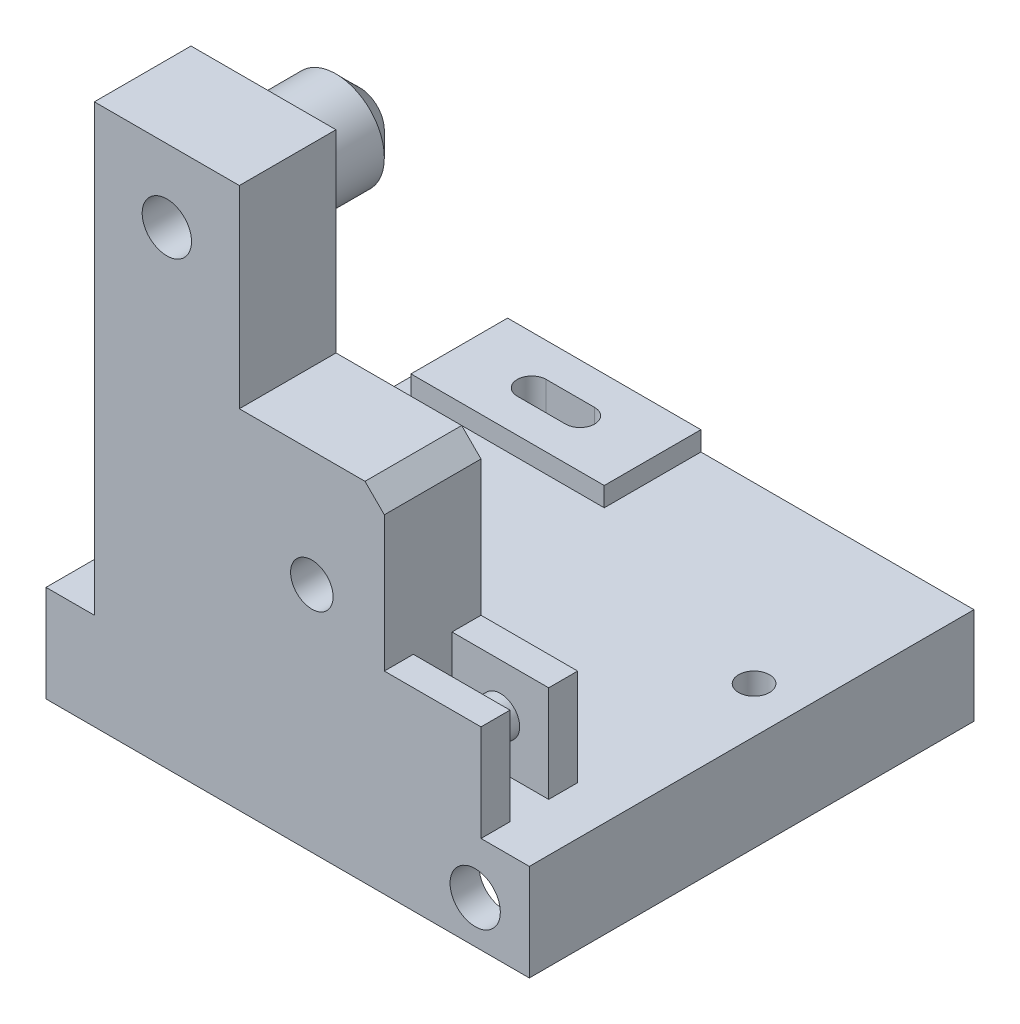
SolidWorks part; units mm, degrees
ref_plane "Front Plane" through (0, 0, 0) normal (0, 0, 1) x (1, 0, 0)
ref_plane "Top Plane" through (0, 0, 0) normal (0, 1, 0) x (1, 0, 0)
ref_plane "Right Plane" through (0, 0, 0) normal (1, 0, 0) x (0, 0, -1)
sketch "Sketch1" plane through (0, 0, 0) normal (0, 0, 1) x (1, 0, 0)
  line L0 (-15, 0) -> (-15, 46)
  line L1 (-15, 46) -> (0, 46)
  line L2 (0, 46) -> (0, 26)
  line L5 (0, 26) -> (15, 26)
  line L6 (15, 26) -> (15, 0)
  line L12 (-15, 0) -> (15, 0)
  circle A0 centre (-7.5, 38.5) radius 2.55
  circle A1 centre (7.5, 14) radius 2.2
  point P8 (0, 0)
  point P12 (-7.5, 46)
  point P16 (7.5, 26)
  dimension "D7" = 5.1
  dimension "D9" = 4.4
  dimension "D1" = 46
  dimension "D2" = 15
  dimension "D3" = 30
  dimension "D6" = 20
  dimension "D8" = 7.5
  dimension "D10" = 12
extrude "Boss-Extrude1" add sketch "Sketch1" along normal blind 6 and the other way blind 4
sketch "Sketch2" plane through (15, 0, 0) normal (1, 0, 0) x (0, 0, -1)
  line L0 (-6, 0) -> (4, 0) construction
  line L1 (-6, 0) -> (-6, 26) construction
  circle A0 centre (-1, 5) radius 2.5
  dimension "D1" = 5
  dimension "D2" = 5
  dimension "D3" = 5
extrude "Boss-Extrude2" [suppressed] add sketch "Sketch2" along normal blind 6
sketch "Sketch3" [suppressed] plane through (21, 0, 0) normal (1, 0, 0) x (0, 0, -1)
  circle A0 centre (-5, 5) radius 4.5
  circle A1 centre (-5, 5) radius 2.5
  circle A2 centre (-5, 5) radius 2.5 construction
  dimension "D1" = 0
  dimension "D2" = 2
extrude "Boss-Extrude3" [suppressed] add sketch "Sketch3" along normal blind 2
ref_plane "Plane1" through (0, 0, -4) normal (0, 0, -1) x (-1, 0, 0)
sketch "Sketch4" plane through (0, 0, -4) normal (0, 0, -1) x (-1, 0, 0)
  line L0 (-15, 0) -> (-15, 10)
  line L1 (-15, 0) -> (-25, 0)
  line L2 (-15, 10) -> (-25, 10)
  line L3 (-25, 0) -> (-25, 10)
  line L4 (-15, 0) -> (-15, 26) construction
  dimension "D1" = 10
  dimension "D2" = 10
extrude "Boss-Extrude4" add sketch "Sketch4" against normal blind 10
sketch "Sketch5" plane through (25, 0, 0) normal (1, 0, 0) x (0, 0, -1)
  line L0 (-3, 10) -> (1, 10)
  line L1 (-3, 10) -> (-3, 0)
  line L2 (1, 10) -> (1, 0)
  line L3 (-3, 0) -> (1, 0)
  line L4 (-6, 10) -> (4, 10) construction
  line L5 (-6, 0) -> (4, 0) construction
  line L7 (-6, 10) -> (4, 10) construction
  point P8 (-1, 10)
  dimension "D1" = 4
extrude "Cut-Extrude1" cut sketch "Sketch5" against normal up to surface (10 mm away) up to face at (15, 18, 1)
sketch "Sketch6" plane through (0, 0, -1) normal (0, 0, 1) x (1, 0, 0)
  line L0 (25, 10) -> (25, 0) construction
  line L1 (15, 10) -> (25, 10) construction
  circle A0 centre (20, 5) radius 2
  dimension "D1" = 4
  dimension "D2" = 5
  dimension "D3" = 5
extrude "Boss-Extrude5" add sketch "Sketch6" along normal up to next
fillet "Fillet1" [suppressed] radius 2
chamfer "Chamfer1" distance 2 angle 45 1 edges at (15, 26, 1)
sketch "Sketch7" plane through (0, 0, 0) normal (0, -1, 0) x (1, 0, 0)
  line L1 (25, 6) -> (-15, 6) construction
  line L2 (25, 6) -> (25, -9.5) construction
  line L3 (25, -9.5) -> (-15, -9.5) construction
  line L4 (-15, 6) -> (-15, -9.5) construction
  line L5 (-15, 6) -> (-15, -4) construction
  line L12 (30, -14.5) -> (-20, -14.5)
  line L24 (-22, -4) -> (22, -4) construction
  line L32 (30, 11) -> (-20, 11) construction
  line L33 (-20, 11) -> (-20, -14.5) construction
  line L34 (30, 11) -> (30, -14.5) construction
  line L35 (-20, -14.5) -> (-20, 6)
  line L36 (-20, 6) -> (30, 6)
  line L37 (30, 6) -> (30, -14.5)
  line L38 (-15, 6) -> (25, 6) construction
  dimension "D2" = 5.5
  dimension "D1" = 5
extrude "Boss-Extrude6" add sketch "Sketch7" along normal blind 10
sketch "Sketch12" plane through (0, 0, 0) normal (0, 1, 0) x (1, 0, 0)
  line L0 (-15, 4) -> (25, 4) construction
  line L3 (-20, 9) -> (-2.5, 9) construction
  line L4 (-20, -6) -> (-20, 14.5) construction
  line L5 (-10.75, 10.5) -> (-5.75, 10.5)
  line L6 (-10.75, 7.5) -> (-5.75, 7.5)
  circle A2 centre (-8.25, 9) radius 1.5 construction
  arc A3 (-10.75, 10.5) -> (-10.75, 7.5) centre (-10.75, 9) ccw
  arc A4 (-5.75, 10.5) -> (-5.75, 7.5) centre (-5.75, 9) cw
  point P12 (-8.25, 7.5)
  point P13 (-8.25, 10.5)
  point P14 (-11.25, 9)
  dimension "D1" = 3
  dimension "D2" = 3
  dimension "D3" = 17.5
  dimension "D4" = 5
  dimension "D5" = 5
sketch "Sketch13" plane through (0, 0, -14.5) normal (0, 0, -1) x (-1, 0, 0)
  line L1 (-30, 0) -> (20, 0)
  line L2 (-30, 0) -> (-30, -10)
  line L3 (-30, -10) -> (20, -10)
  line L4 (20, 0) -> (20, -10)
extrude "Boss-Extrude9" add sketch "Sketch13" along normal blind 25.5
sketch "Sketch14" plane through (0, 0, 0) normal (0, 1, 0) x (1, 0, 0)
  line L0 (-20, 22) -> (30, 22) construction
  line L3 (30, 40) -> (30, -6) construction
  line L4 (-20, -6) -> (-20, 40) construction
  line L7 (0, 4) -> (-15, 4) construction
  dimension "D1" = 18
ref_plane "Plane2" through (0, 0, -22) normal (0, 0, -1) x (-1, 0, 0)
sketch "Sketch16" plane through (0, -10, 0) normal (0, -1, 0) x (1, 0, 0)
  line L8 (27, -37) -> (27, 3)
  line L9 (27, -37) -> (27, 3)
  line L10 (-17, -37) -> (27, -37)
  line L11 (27, 3) -> (-17, 3)
  line L14 (-17, -37) -> (27, -37)
  line L16 (27, 3) -> (-17, 3)
  line L17 (-17, 3) -> (-17, -37)
  line L18 (-17, 3) -> (-17, -37)
  dimension "D1" = 3
extrude "Cut-Extrude3" cut sketch "Sketch16" against normal blind 7
sketch "Sketch17" plane through (0, 0, 6) normal (0, 0, 1) x (1, 0, 0)
  line L1 (-20, 0) -> (30, 0) construction
  line L2 (30, -10) -> (30, 0) construction
  circle A0 centre (24.4, -5.6) radius 2.6
  dimension "D1" = 5.2
  dimension "D2" = 5.6
  dimension "D3" = 5.6
extrude "Cut-Extrude4" cut sketch "Sketch17" against normal up to surface (3 mm away) up to face at (5, -6.5, 3)
sketch "Sketch18" plane through (-20, 0, 0) normal (-1, 0, 0) x (0, 0, 1)
  line L1 (-9, -10) -> (-11, -10)
  line L2 (-9, -10) -> (-9, 0)
  line L3 (-9, 0) -> (-11, 0)
  line L4 (-11, -10) -> (-11, 0)
  line L6 (-40, -10) -> (-40, 0) construction
  line L7 (6, 0) -> (-40, 0) construction
  line L8 (6, -10) -> (-40, -10) construction
  dimension "D1" = 2
  dimension "D2" = 29
extrude "Boss-Extrude11" add sketch "Sketch18" along normal blind 5
fillet "Fillet2" radius 5 1 edges at (-20, -5, -11)
ref_plane "Plane3" through (-7.5, 0, 0) normal (1, 0, 0) x (0, 0, -1)
sketch "Sketch19" plane through (-7.5, 0, 0) normal (-1, 0, 0) x (0, 0, 1)
  line L0 (-4, 38.5) -> (-14, 38.5)
  line L1 (-4, 46) -> (-4, 0) construction
  line L2 (-11.5, 43.5) -> (-4, 43.5)
  line L3 (-4, 43.5) -> (-4, 38.5)
  line L4 (-4, 46) -> (6, 46) construction
  line L5 (-14, 38.5) -> (-14, 41)
  line L6 (-11.5, 43.5) -> (-14, 41)
  dimension "D2" = 135
  dimension "D1" = 7.5
  dimension "D3" = 10
  dimension "D4" = 5
  dimension "D5" = 2.5
revolve "Revolve1" add sketch "Sketch19" angle 360 about L0
sketch "Sketch20" plane through (0, 0, -4) normal (0, 0, 1) x (1, 0, 0)
  circle A1 centre (-7.5, 38.5) radius 2.55
  circle A2 centre (-7.5, 38.5) radius 2.55
  dimension "D1" = 0
extrude "Cut-Extrude5" cut sketch "Sketch20" against normal up to next
fillet "Fillet5" radius 1.5 1 edges at (-12.5, 38.5, -4)
extrude "Cut-Extrude6" cut sketch "Sketch12" against normal blind 3 contours A4 L6 A3 L5
sketch "Sketch22" plane through (0, 0, 0) normal (0, 1, 0) x (1, 0, 0)
  line L0 (22, 4) -> (-22, 4) construction
  line L1 (-18.25, 14) -> (1.75, 14)
  line L2 (-18.25, 14) -> (-18.25, 4)
  line L3 (-18.25, 4) -> (1.75, 4)
  line L4 (1.75, 14) -> (1.75, 4)
  line L5 (-8.25, 4) -> (-8.25, 14) construction
  line L6 (-10.75, 7.5) -> (-5.75, 7.5) construction
  line L7 (-10.75, 10.5) -> (-5.75, 10.5) construction
  line L8 (-10.75, 7.5) -> (-5.75, 7.5)
  line L9 (-10.75, 10.5) -> (-5.75, 10.5)
  line L10 (5.5, 22) -> (-5.5, 22) construction
  line L11 (-10.75, 36.5) -> (-5.75, 36.5)
  line L12 (-10.75, 33.5) -> (-5.75, 33.5)
  line L13 (-18.25, 40) -> (1.75, 40)
  line L14 (1.75, 30) -> (1.75, 40)
  line L15 (-18.25, 30) -> (1.75, 30)
  line L16 (-18.25, 30) -> (-18.25, 40)
  arc A0 (-10.75, 33.5) -> (-10.75, 36.5) centre (-10.75, 35) cw
  arc A2 (-5.75, 7.5) -> (-5.75, 10.5) centre (-5.75, 9) ccw construction
  arc A3 (-10.75, 10.5) -> (-10.75, 7.5) centre (-10.75, 9) ccw construction
  arc A4 (-5.75, 7.5) -> (-5.75, 10.5) centre (-5.75, 9) ccw
  arc A5 (-10.75, 10.5) -> (-10.75, 7.5) centre (-10.75, 9) ccw
  arc A6 (-5.75, 36.5) -> (-5.75, 33.5) centre (-5.75, 35) cw
  point P15 (-8.25, 10.5)
  dimension "D1" = 20
  dimension "D2" = 10
extrude "Boss-Extrude12" add sketch "Sketch22" along normal blind 2
mirror "Mirror2" [suppressed] about plane through (0, 0, -22) normal (0, 0, -1)
sketch "Sketch23" plane through (0, 0, 0) normal (0, 1, 0) x (1, 0, 0)
  line L0 (-20, 22) -> (30, 22) construction
  line L1 (30, 40) -> (30, -6) construction
  circle A0 centre (25.25, 22) radius 1.6
  dimension "D1" = 3.2
  dimension "D2" = 4.75
extrude "Cut-Extrude7" cut sketch "Sketch23" against normal up to next
sketch "Sketch24" plane through (0, 0, 0) normal (0, 1, 0) x (1, 0, 0)
  line L2 (-10.75, 33.5) -> (-5.75, 33.5)
  line L6 (-10.75, 33.5) -> (-5.75, 33.5)
  line L7 (-5.75, 36.5) -> (-10.75, 36.5)
  line L8 (-5.75, 36.5) -> (-10.75, 36.5)
  arc A1 (-10.75, 36.5) -> (-10.75, 33.5) centre (-10.75, 35) ccw
  arc A6 (-10.75, 36.5) -> (-10.75, 33.5) centre (-10.75, 35) ccw
  arc A7 (-5.75, 33.5) -> (-5.75, 36.5) centre (-5.75, 35) ccw
  arc A8 (-5.75, 33.5) -> (-5.75, 36.5) centre (-5.75, 35) ccw
  dimension "D1" = 0
extrude "Cut-Extrude8" cut sketch "Sketch24" against normal through all
